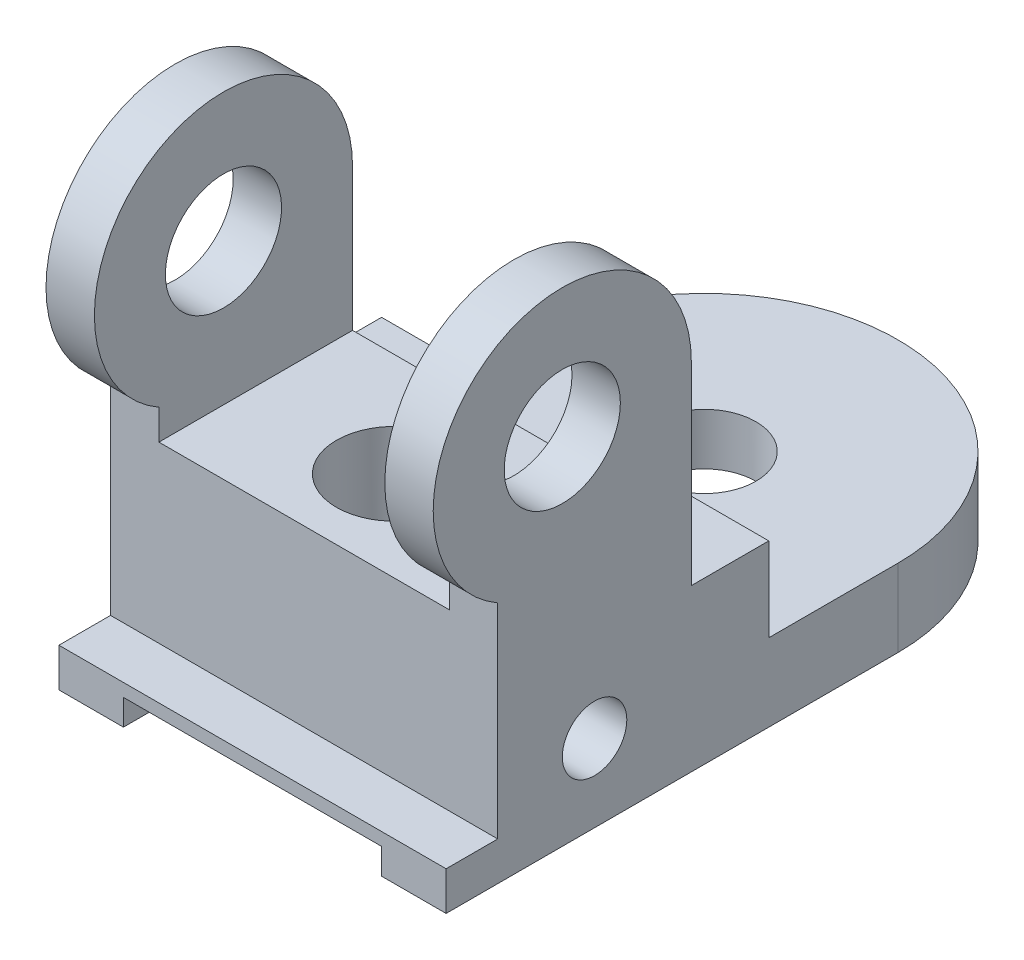
SolidWorks part; units mm, degrees
ref_plane "Plan de face" through (0, 0, 0) normal (0, 0, 1) x (1, 0, 0)
ref_plane "Plan de dessus" through (0, 0, 0) normal (0, 1, 0) x (1, 0, 0)
ref_plane "Plan de droite" through (0, 0, 0) normal (1, 0, 0) x (0, 0, -1)
sketch "Esquisse2" plane through (0, 0, 0) normal (1, 0, 0) x (0, 0, -1)
  line L0 (0, -25.5) -> (-50, -25.5)
  line L1 (-100, -37.5) -> (0, -37.5)
  line L2 (-100, -37.5) -> (-100, -31.5)
  line L4 (0, -37.5) -> (0, -25.5)
  line L5 (-100, -37.5) -> (59.9811, 22.4929) construction
  line L6 (0, 12.659) -> (0, -37.5) construction
  line L7 (-50, -25.5) -> (-50, -12.5)
  line L8 (-50, -12.5) -> (-62, -12.5)
  line L9 (-62, -12.5) -> (-62, 17.5)
  line L10 (-92, 0.1795) -> (-92, -31.5)
  line L11 (-92, -31.5) -> (-100, -31.5)
  arc A0 (-62, 17.5) -> (-92, 0.1795) centre (-82, 17.5) ccw
  circle A1 centre (-82, 17.5) radius 9
  circle A2 centre (-77, -25.5) radius 5
  point P0 (0, 0)
  point P9 (36.2158, -37.5)
  point P14 (-25.1968, 17.5)
  point P16 (-88.339, 0)
  point P20 (-2.9921, -37.5)
  point P22 (0, -37.5)
  dimension "D6" = 40
  dimension "D7" = 18
  dimension "D8" = 43
  dimension "D9" = 10
  dimension "D2" = 100
  dimension "D3" = 12
  dimension "D4" = 13
  dimension "D5" = 12
  dimension "D10" = 50
  dimension "D11" = 6
  dimension "D12" = 30
  dimension "D13" = 15
  dimension "D14" = 17.5
  dimension "D15" = 12.5
extrude "Boss.-Extru.1" add sketch "Esquisse2" along normal blind 60
sketch "Esquisse3" plane through (0, 0, 62) normal (0, 0, -1) x (-1, 0, 0)
  line L0 (-60, -37.5) -> (0, -37.5) construction
  line L1 (-50, -33.5) -> (-10, -33.5)
  line L2 (-50, -33.5) -> (-50, -37.5)
  line L3 (-50, -37.5) -> (-10, -37.5)
  line L4 (-10, -33.5) -> (-10, -37.5)
  line L5 (-50, -33.5) -> (-10, -37.5) construction
  line L6 (-50, -37.5) -> (-10, -33.5) construction
  line L7 (0, 37.5) -> (-60, 37.5) construction
  line L8 (-52.5, 37.5) -> (-7.5, 37.5)
  line L9 (-52.5, 37.5) -> (-52.5, -4.5)
  line L10 (-52.5, -4.5) -> (-7.5, -4.5)
  line L11 (-7.5, 37.5) -> (-7.5, -4.5)
  line L12 (-60, 37.5) -> (-60, 0.1795) construction
  point P0 (-30, -35.5)
  dimension "D1" = 40
  dimension "D2" = 4
  dimension "D3" = 10
  dimension "D4" = 7.5
  dimension "D5" = 7.5
  dimension "D6" = 42
extrude "Enlèv. mat.-Extru.1" cut sketch "Esquisse3" against normal mid plane 170
fillet "Congé1" 2 edges at (60, -31.5, 0) (0, -31.5, 0) type full round first side face at (60, 17.5, 73) second side face at (0, -17.034, 62.3) middle face at (30, -33.5, 0)
sketch "Esquisse4" plane through (0, -4.5, 0) normal (0, 1, 0) x (1, 0, 0)
  line L0 (52.5, -92) -> (7.5, -92) construction
  line L2 (7.5, -92) -> (7.5, -62) construction
  circle A0 centre (30, -78) radius 9
  circle A1 centre (30, -30) radius 8.0015
  point P7 (0, 0)
  point P9 (7.5, -75.462)
  point P11 (0, 0)
  dimension "D1" = 18
  dimension "D2" = 16.0029
  dimension "D3" = 14
  dimension "D4" = 22.5
extrude "Enlèv. mat.-Extru.2" cut sketch "Esquisse4" against normal mid plane 170
sketch "Esquisse5" plane through (0, 0, 50) normal (0, 0, -1) x (-1, 0, 0)
  line L0 (-60, -12.5) -> (0, -12.5) construction
  circle A0 centre (-30, -12.5) radius 13
  dimension "D1" = 26
extrude "Enlèv. mat.-Extru.3" cut sketch "Esquisse5" against normal up to surface (12 mm away) up to face at (30, 4.5, 62)
